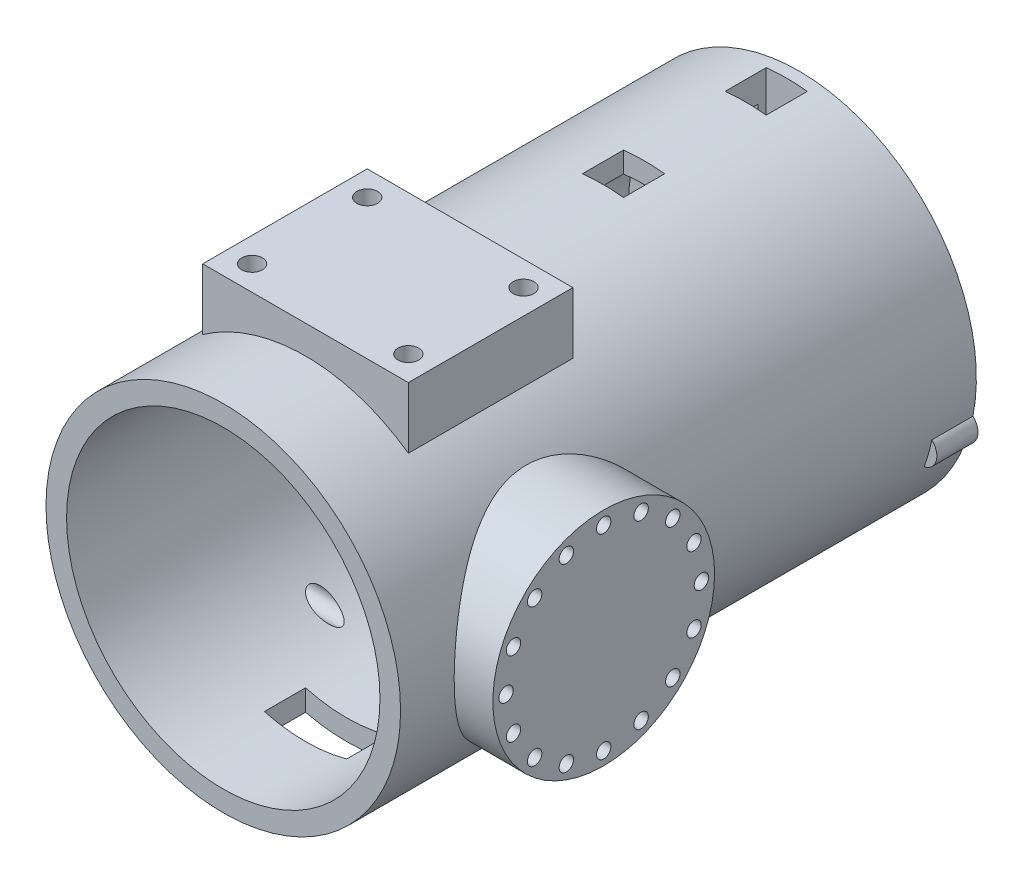
SolidWorks part; units mm, degrees
other "Markup1"
sketch "Sketch14" plane through (-43.1, 43.1, 140) normal (-0.1765, 0.0048, 0.9843) x (0.9842, -0.0149, 0.1765)
other "Markup2"
sketch "Sketch23" plane through (45.1, -43.1, 140) normal (0.9491, -0.0629, 0.3087) x (0.311, 0.031, -0.9499)
ref_plane "Front Plane" through (0, 0, 0) normal (0, 0, 1) x (1, 0, 0)
ref_plane "Top Plane" through (0, 0, 0) normal (0, 1, 0) x (1, 0, 0)
ref_plane "Right Plane" through (0, 0, 0) normal (1, 0, 0) x (0, 0, -1)
sketch "Sketch1" plane through (0, 0, 0) normal (0, 0, 1) x (1, 0, 0)
  circle A1 centre (0, 0) radius 43.1
  dimension "D1" = 86.2
extrude "Main Body" add sketch "Sketch1" along normal blind 140
ref_plane "Plane1" through (0, 43.1, 0) normal (0, 1, 0) x (1, 0, 0)
sketch "Sketch34" plane through (0, 43.1, 0) normal (0, 1, 0) x (1, 0, 0)
  line L6 (-5, -13) -> (5, -13)
  line L8 (-5, -13) -> (-5, -3)
  line L9 (-5, -3) -> (5, -3)
  line L10 (5, -13) -> (5, -3)
  line L11 (-5, -13) -> (5, -3) construction
  line L12 (-5, -3) -> (5, -13) construction
  point P0 (0, -8)
  dimension "D1" = 8
  dimension "D2" = 10
  dimension "D3" = 10
sketch "Sketch6" plane through (0, 43.1, 0) normal (0, 1, 0) x (1, 0, 0)
  line L2 (-5, -47.7) -> (5, -47.7)
  line L3 (-5, -47.7) -> (-5, -37.7)
  line L4 (-5, -37.7) -> (5, -37.7)
  line L5 (5, -47.7) -> (5, -37.7)
  line L6 (-5, -47.7) -> (5, -37.7) construction
  line L7 (-5, -37.7) -> (5, -47.7) construction
  point P2 (0, -42.7)
  dimension "D2" = 10
  dimension "D1" = 42.7
  dimension "D3" = 10
extrude "Cut-Extrude3" cut sketch "Sketch6" against normal through all
ref_plane "Plane2" through (52.5, 0, 0) normal (1, 0, 0) x (0, 0, -1)
sketch "Sketch8" plane through (52.5, 0, 0) normal (1, 0, 0) x (0, 0, -1)
  circle A0 centre (-100, 0) radius 26.95
  dimension "D1" = 53.9
  dimension "D2" = 100
extrude "Boss-Extrude2" add sketch "Sketch8" against normal blind 20
mirror "Mirror1" [suppressed] about plane through (0, 0, 0) normal (1, 0, 0)
ref_plane "Plane3" through (0, 50, 0) normal (0, 1, 0) x (1, 0, 0)
sketch "Sketch33" plane through (0, 50, 0) normal (0, 1, 0) x (1, 0, 0)
  line L1 (-25, -120) -> (25, -120)
  line L2 (-25, -120) -> (-25, -80)
  line L3 (-25, -80) -> (25, -80)
  line L4 (25, -120) -> (25, -80)
  line L5 (-25, -120) -> (25, -80) construction
  line L6 (-25, -80) -> (25, -120) construction
  point P0 (0, -100)
  dimension "D1" = 100
  dimension "D2" = 40
  dimension "D3" = 50
extrude "Boss-Extrude11" add sketch "Sketch33" against normal blind 22
sketch "Sketch35" plane through (0, 50, 0) normal (0, 1, 0) x (1, 0, 0)
  line L0 (-25, -120) -> (-25, -80) construction
  line L1 (25, -120) -> (25, -80) construction
  line L2 (25, -80) -> (-25, -80) construction
  line L3 (-25, -120) -> (25, -120) construction
  circle A0 centre (-19, -86) radius 2.525
  circle A1 centre (19, -86) radius 2.525
  circle A2 centre (-19, -114) radius 2.525
  circle A3 centre (19, -114) radius 2.525
  dimension "D1" = 5.05
  dimension "D2" = 6
  dimension "D3" = 6
  dimension "D4" = 6
  dimension "D5" = 6
extrude "Cut-Extrude14" cut sketch "Sketch35" against normal blind 4
sketch "Sketch5" plane through (0, 0, 140) normal (0, 0, 1) x (1, 0, 0)
  circle A0 centre (0, 0) radius 31.75
  dimension "D1" = 63.5
extrude "Hole 1" cut sketch "Sketch5" against normal through all
sketch "Sketch10" plane through (0, 0, 0) normal (0, 1, 0) x (1, 0, 0)
  line L0 (43.1, 0) -> (-43.1, 0) construction
  line L1 (-10, -120) -> (10, -120)
  line L2 (-10, -120) -> (-10, -110)
  line L3 (-10, -110) -> (10, -110)
  line L4 (10, -120) -> (10, -110)
  line L5 (-10, -120) -> (10, -110) construction
  line L6 (-10, -110) -> (10, -120) construction
  point P0 (0, -115)
  point P7 (-10, -115)
  dimension "D1" = 110
  dimension "D2" = 10
  dimension "D3" = 20
extrude "Motor Wire Hole" cut sketch "Sketch10" against normal through all
sketch "Sketch27" plane through (0, 0, 0) normal (1, 0, 0) x (0, 0, -1)
  line L1 (-100, -36.5) -> (-60, -36.5)
  line L2 (-100, -36.5) -> (-100, -27.5)
  line L3 (-100, -27.5) -> (-60, -27.5)
  line L4 (-60, -36.5) -> (-60, -27.5)
  dimension "D1" = 60
  dimension "D2" = 27.5
  dimension "D3" = 40
  dimension "D4" = 9
extrude "Boss-Extrude9" add sketch "Sketch27" along normal blind 33 and the other way blind 33
sketch "Sketch11" plane through (0, 0, 0) normal (1, 0, 0) x (0, 0, -1)
  circle A0 centre (-65, -32) radius 2.5
  circle A1 centre (-95, -32) radius 2.5
  dimension "D3" = 5
  dimension "D1" = 65
  dimension "D2" = 32
  dimension "D4" = 30
extrude "Cut-Extrude6" cut sketch "Sketch11" against normal through all both and the other way through all
sketch "Sketch28" plane through (-33, 0, 0) normal (-1, 0, 0) x (0, 0, 1)
  line L0 (62.9793, -28.5) -> (67.0207, -28.5)
  line L1 (67.0207, -28.5) -> (69.0415, -32)
  line L2 (69.0415, -32) -> (67.0207, -35.5)
  line L3 (67.0207, -35.5) -> (62.9793, -35.5)
  line L4 (62.9793, -35.5) -> (60.9585, -32)
  line L6 (60.9585, -32) -> (62.9793, -28.5)
  line L7 (92.9793, -28.5) -> (97.0207, -28.5)
  line L8 (97.0207, -28.5) -> (99.0415, -32)
  line L9 (99.0415, -32) -> (97.0207, -35.5)
  line L10 (97.0207, -35.5) -> (92.9793, -35.5)
  line L11 (92.9793, -35.5) -> (90.9585, -32)
  line L12 (90.9585, -32) -> (92.9793, -28.5)
  circle A0 centre (65, -32) radius 3.5 construction
  circle A1 centre (65, -32) radius 2.5 construction
  circle A2 centre (95, -32) radius 3.5 construction
  circle A3 centre (95, -32) radius 2.5 construction
  dimension "D1" = 7
  dimension "D2" = 7
extrude "Cut-Extrude7" cut sketch "Sketch28" against normal blind 3
sketch "Sketch29" plane through (33, 0, 0) normal (1, 0, 0) x (0, 0, -1)
  circle A0 centre (-95, -32) radius 3.5
  circle A1 centre (-65, -32) radius 3.5
  dimension "D1" = 7
extrude "Cut-Extrude8" cut sketch "Sketch29" against normal blind 4
sketch "Sketch2" plane through (0, 0, 140) normal (0, 0, 1) x (1, 0, 0)
  circle A0 centre (0, 0) radius 38.1
  dimension "D1" = 76.2
extrude "Cut-Extrude5" cut sketch "Sketch2" against normal blind 135
sketch "Sketch9" plane through (0, 0, 5) normal (0, 0, 1) x (1, 0, 0)
  circle A0 centre (0, 0) radius 38.1
  circle A1 centre (0, 0) radius 36.44
  dimension "D1" = 76.2
  dimension "D2" = 1.66
extrude "Boss-Extrude3" add sketch "Sketch9" along normal blind 10
extrude "Cut-Extrude13" cut sketch "Sketch34" against normal blind 15
sketch "Sketch30" plane through (52.5, 0, 0) normal (1, 0, 0) x (0, 0, -1)
  line L0 (-100, 23.75) -> (-100, 0) construction
  circle A0 centre (-100, 0) radius 23.75 construction
  circle A1 centre (-100, 23.75) radius 1.75
  circle A2 centre (-90.9113, 21.9421) radius 1.75
  circle A3 centre (-83.2062, 16.7938) radius 1.75
  circle A4 centre (-78.0579, 9.0887) radius 1.75
  circle A5 centre (-76.25, 0) radius 1.75
  circle A6 centre (-78.0579, -9.0887) radius 1.75
  circle A7 centre (-83.2062, -16.7938) radius 1.75
  circle A8 centre (-90.9113, -21.9421) radius 1.75
  circle A9 centre (-100, -23.75) radius 1.75
  circle A10 centre (-109.0887, -21.9421) radius 1.75
  circle A11 centre (-116.7938, -16.7938) radius 1.75
  circle A12 centre (-121.9421, -9.0887) radius 1.75
  circle A13 centre (-123.75, 0) radius 1.75
  circle A14 centre (-121.9421, 9.0887) radius 1.75
  circle A15 centre (-116.7938, 16.7938) radius 1.75
  circle A16 centre (-109.0887, 21.9421) radius 1.75
  point P38 (-100, 0)
  dimension "D1" = 47.5
  dimension "D2" = 3.5
  dimension "D3" = 16
extrude "Cut-Extrude9" cut sketch "Sketch30" against normal up to surface (22.7083 mm away) up to face at (38.1, 0, 15)
sketch "Sketch31" plane through (52.5, 0, 0) normal (1, 0, 0) x (0, 0, -1)
  line L0 (0, -43.1) -> (0, 43.1) construction
  line L1 (0, -15) -> (-10, -15)
  line L2 (0, -15) -> (0, -7.5)
  line L3 (0, -7.5) -> (-10, -7.5)
  line L4 (-10, -15) -> (-10, -7.5)
  dimension "D1" = 15
  dimension "D2" = 7.5
  dimension "D3" = 10
extrude "Boss-Extrude10" add sketch "Sketch31" against normal up to body from offset 9 offset against normal yes
sketch "Sketch32" plane through (0, 0, 0) normal (0, 0, -1) x (-1, 0, 0)
  line L0 (-43.5, -11.25) -> (-29.6901, -11.25) construction
  line L1 (-43.5, -15) -> (-43.5, -7.5) construction
  line L3 (-42.4424, -7.5) -> (-43.5, -7.5) construction
  line L5 (-43.5, -15) -> (-43.5, -7.5)
  line L6 (-43.5, -7.5) -> (-42.4424, -7.5)
  circle A0 centre (0, 0) radius 31.75 construction
  arc A2 (-40.4056, -15) -> (-42.4424, -7.5) centre (0, 0) ccw construction
  arc A3 (-40.4056, -15) -> (-42.2658, -8.4385) centre (-39.6806, -11.25) cw
  arc A4 (-42.2658, -8.4385) -> (-42.4424, -7.5) centre (0, 0) cw
  line M3 (-42.4424, -7.5) -> (-43.5, -7.5)
  line M4 (-43.5, -7.5) -> (-43.5, -15)
  line M5 (-43.5, -15) -> (-40.4056, -15)
extrude "Cut-Extrude10" cut sketch "Sketch32" against normal up to surface (10 mm away) contours M4 M3 | L5 M5 region at (43.0347, -8.5479, 0) region at (42.7123, -14.1508, 0) up to face at (42.5043, -11.2615, 10)
